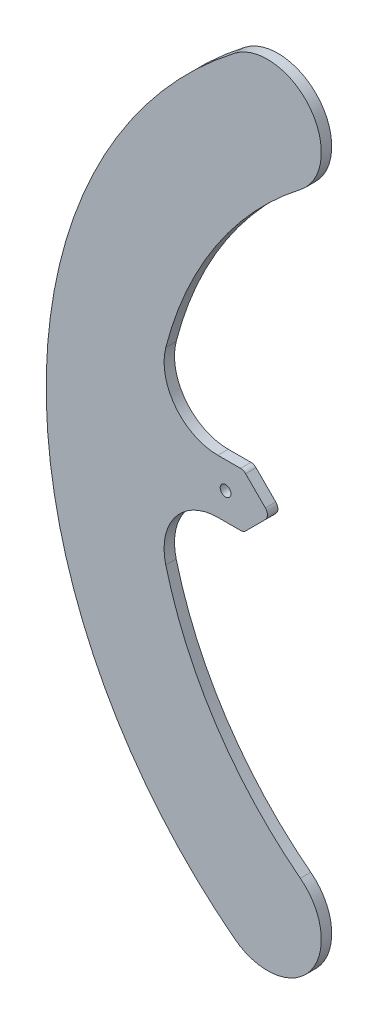
SolidWorks part; units mm, degrees
ref_plane "Front Plane" through (0, 0, 0) normal (0, 0, 1) x (1, 0, 0)
ref_plane "Top Plane" through (0, 0, 0) normal (0, 1, 0) x (1, 0, 0)
ref_plane "Right Plane" through (0, 0, 0) normal (1, 0, 0) x (0, 0, -1)
sketch "Sketch1" plane through (0, 0, 0) normal (0, 0, 1) x (1, 0, 0)
  line L0 (-32.8019, 0) -> (18.2589, 0) construction
  line L1 (70.5, 105) -> (70.5, 135) construction
  line L2 (205.5, -110) -> (-64.5, -110)
  line L3 (205.5, -110) -> (205.5, 110)
  line L4 (205.5, 110) -> (-64.5, 110)
  line L5 (-19.5, 6.5) -> (-19.5, -6.5)
  line L6 (-18.5, -7.5) -> (-9.5, -7.5)
  line L7 (-9.5, -7.5) -> (-2, 0)
  line L8 (-2, 0) -> (-9.5, 7.5)
  line L9 (-9.5, 7.5) -> (-18.5, 7.5)
  line L10 (-19.5, 6.5) -> (-19.5, -6.5)
  line L11 (-18.5, -7.5) -> (-9.5, -7.5)
  line L12 (-9.5, -7.5) -> (-2, 0)
  line L13 (-2, 0) -> (-9.5, 7.5)
  line L15 (-64.5, -110) -> (-64.5, 110)
  line L16 (205.5, -110) -> (-64.5, 110) construction
  line L17 (205.5, 110) -> (-64.5, -110) construction
  line L18 (-18, 7.5) -> (-34.2318, 7.5)
  line L19 (-18.5, -7.5) -> (-34.2318, -7.5)
  line L146 (-9.5, 7.5) -> (-18.5, 7.5)
  circle A0 centre (-14.5, 0) radius 1.5 construction
  arc A2 (-19.5, -6.5) -> (-18.5, -7.5) centre (-18.5, -6.5) ccw
  circle A6 centre (-14.5, 0) radius 1.5
  circle A7 centre (-14.5, 0) radius 1.5
  circle A8 centre (70.5, 0) radius 135
  circle A9 centre (70.5, 0) radius 105
  circle A11 centre (-2.8144, 95) radius 15
  circle A12 centre (-2.8144, -95) radius 15
  arc A32 (-19.5, -6.5) -> (-18.5, -7.5) centre (-18.5, -6.5) ccw
  arc A65 (-18.5, 7.5) -> (-19.5, 6.5) centre (-18.5, 6.5) ccw
  arc A66 (-18.5, 7.5) -> (-19.5, 6.5) centre (-18.5, 6.5) ccw
  point P19 (-64.5, 0)
  point P27 (70.5, 110)
  dimension "D3" = 270
  dimension "D5" = 30
  dimension "D2" = 55
  dimension "D4" = 220
  dimension "D1" = 0
extrude "Boss-Extrude1" add sketch "Sketch1" along normal blind 2.9 contours A11 | A8 A12 A9 A11 | A12 | L18 A9 L19 L10 | L146 L10 L11 L12 L13 A6 region at (-2.8144, -95, 0) region at (-37.1858, 0, 0) region at (-2.8144, 95, 0) region at (-26.9408, 0, 0) region at (-12.3671, 0, 0)
fillet "Fillet1" radius 15 2 edges at (-34.2318, -7.5, 1.45) (-34.2318, 7.5, 1.45)
fillet "Fillet2" radius 2 3 edges at (-9.5, -7.5, 1.45) (-9.5, 7.5, 1.45) (-2, 0, 1.45)
